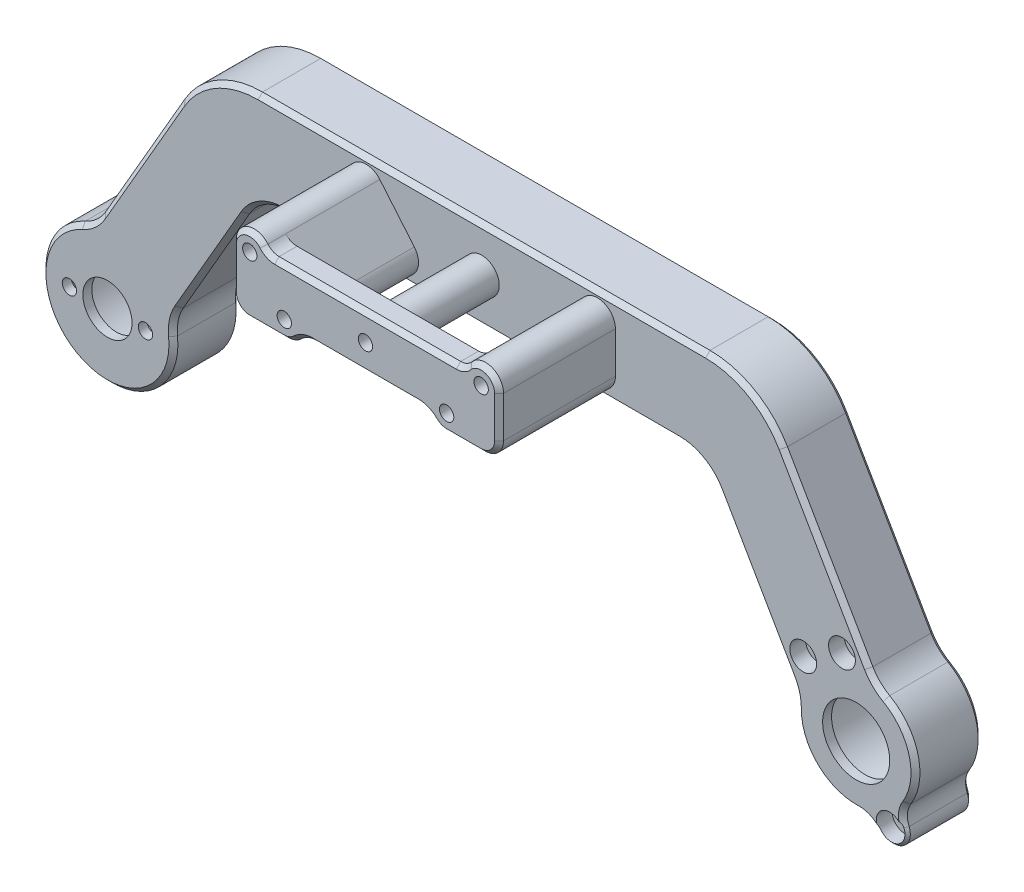
SolidWorks part; units mm, degrees
other "Markup1"
sketch "Sketch2"
ref_plane "Front Plane" through (0, 0, 0) normal (0, 0, 1) x (1, 0, 0)
ref_plane "Top Plane" through (0, 0, 0) normal (0, 1, 0) x (1, 0, 0)
ref_plane "Right Plane" through (0, 0, 0) normal (1, 0, 0) x (0, 0, -1)
ref_axis "X" through (-88.99, 0, 0) along (1, 0, 0)
ref_axis "Y" through (0, 55, 0) along (0, -1, 0)
ref_axis "Z" through (0, 0, -88.99) along (0, 0, 1)
sketch "Sketch1" plane through (0, 0, 0) normal (0, 0, 1) x (1, 0, 0)
  line L0 (0, 10) -> (0, -10) construction
  line L1 (-50, 10) -> (50, 10)
  line L2 (-50, -10) -> (50, -10)
  line L3 (67.3205, 0) -> (92.3205, -43.3013)
  line L4 (75, -53.3013) -> (50, -10)
  line L5 (-75, -53.3013) -> (-50, -10)
  line L6 (-67.3205, 0) -> (-92.3205, -43.3013)
  arc A0 (50, 10) -> (67.3205, 0) centre (50, -10) cw
  arc A1 (92.3205, -43.3013) -> (75, -53.3013) centre (83.6603, -48.3013) cw
  arc A3 (-92.3205, -43.3013) -> (-75, -53.3013) centre (-83.6603, -48.3013) ccw
  arc A4 (-50, 10) -> (-67.3205, 0) centre (-50, -10) ccw
  point P4 (0, 0)
  dimension "D1" = 20
  dimension "D2" = 50
  dimension "D3" = 60
  dimension "D4" = 50
extrude "Boss-Extrude1" add sketch "Sketch1" along normal mid plane 15
ref_plane "Plane1" through (0, 0, 28.5) normal (0, 0, 1) x (1, 0, 0)
sketch "Sketch3" plane through (0, 0, 0) normal (0, 0, 1) x (1, 0, 0)
  line L0 (-22, 0) -> (22, 0) construction
  line L1 (25.8567, 4.5963) -> (18.1433, -4.5963) construction
  line L2 (0, 0) -> (0, 1.6) construction
  line L3 (-25.8567, 4.5963) -> (-18.1433, -4.5963) construction
  circle A1 centre (0, 0) radius 1.6
  circle A2 centre (25.8567, 4.5963) radius 1.6
  circle A3 centre (18.1433, -4.5963) radius 1.6
  circle A4 centre (-25.8567, 4.5963) radius 1.6
  circle A5 centre (-18.1433, -4.5963) radius 1.6
  point P7 (0, 0)
  point P10 (22, 0)
  dimension "D6" = 3.2
  dimension "D3" = 12
  dimension "D4" = 22
  dimension "D5" = 50
extrude "Cut-Extrude1" cut sketch "Sketch3" against normal through all both and the other way through all
sketch "Sketch4" plane through (0, 0, 28.5) normal (0, 0, 1) x (1, 0, 0)
  line L0 (25.8567, 4.5963) -> (18.1433, -4.5963) construction
  line L1 (-25.8567, 4.5963) -> (-18.1433, -4.5963) construction
  line L2 (25.8567, 4.5963) -> (18.1433, -4.5963) construction
  line L3 (-25.8567, 4.5963) -> (-18.1433, -4.5963) construction
  line L4 (15.0791, -2.0251) -> (22.7925, 7.1674)
  line L5 (29.8567, 4.5963) -> (29.8567, -4.5963)
  line L6 (25.8567, -8.5963) -> (18.1433, -8.5963)
  line L7 (0, 0) -> (0, 1.6) construction
  line L8 (0, 0) -> (0, 1.6) construction
  line L9 (-25.8567, -8.5963) -> (-18.1433, -8.5963)
  line L10 (-29.8567, 4.5963) -> (-29.8567, -4.5963)
  line L11 (-15.0791, -2.0251) -> (-22.7925, 7.1674)
  line L12 (20.289, 6) -> (-20.289, 6)
  line L13 (0, 6) -> (0, 3.9)
  line L14 (0, -3.9) -> (0, -6)
  line L15 (-11.8193, -6) -> (11.8193, -6)
  circle A0 centre (25.8567, 4.5963) radius 1.6 construction
  circle A1 centre (18.1433, -4.5963) radius 1.6 construction
  circle A2 centre (-25.8567, 4.5963) radius 1.6 construction
  circle A3 centre (-18.1433, -4.5963) radius 1.6 construction
  circle A4 centre (0, 0) radius 1.6 construction
  circle A5 centre (25.8567, 4.5963) radius 1.6
  circle A6 centre (18.1433, -4.5963) radius 1.6
  circle A7 centre (-25.8567, 4.5963) radius 1.6
  circle A8 centre (-18.1433, -4.5963) radius 1.6
  circle A9 centre (0, 0) radius 1.6
  arc A10 (22.7925, 7.1674) -> (29.8567, 4.5963) centre (25.8567, 4.5963) cw
  arc A11 (29.8567, -4.5963) -> (25.8567, -8.5963) centre (25.8567, -4.5963) cw
  arc A12 (18.1433, -8.5963) -> (15.0791, -2.0251) centre (18.1433, -4.5963) cw
  arc A13 (-29.8567, -4.5963) -> (-25.8567, -8.5963) centre (-25.8567, -4.5963) ccw
  arc A14 (-22.7925, 7.1674) -> (-29.8567, 4.5963) centre (-25.8567, 4.5963) ccw
  arc A15 (-18.1433, -8.5963) -> (-15.0791, -2.0251) centre (-18.1433, -4.5963) ccw
  circle A16 centre (0, 0) radius 3.9
  arc A17 (22.7925, 7.1674) -> (20.289, 6) centre (20.289, 9.2681) cw
  arc A18 (11.8193, -6) -> (15.3326, -7.4424) centre (11.8193, -11) cw
  arc A19 (-11.8193, -6) -> (-15.3326, -7.4424) centre (-11.8193, -11) ccw
  arc A20 (-22.7925, 7.1674) -> (-20.289, 6) centre (-20.289, 9.2681) ccw
  dimension "D1" = 4
  dimension "D4" = 4
  dimension "D5" = 7.8
  dimension "D6" = 12
  dimension "D7" = 5
  dimension "D2" = 4
  dimension "D3" = 4
extrude "Boss-Extrude2" add sketch "Sketch4" against normal up to surface (21 mm away) separate body contours L9 A15 L11 A14 L10 A13 A8 A7 | A12 L6 A11 L5 A10 L4 A6 A5 | A16 A9 region at (23.3022, -1.3358, 28.5) region at (2.6797, 2.6797, 28.5) region at (-23.3022, -1.3358, 28.5) up to face at (-19.7433, -4.5963, 7.5)
extrude "Boss-Extrude3" add sketch "Sketch4<3>" along normal blind 5 contours L9 A15 L11 A14 L10 A13 A8 A7 | A20 L11 A15 A19 L15 L14 A16 L13 L12 | A16 A9 | L15 A18 A12 L4 A17 L12 L13 A16 L14 | A12 L6 A11 L5 A10 L4 A6 A5 region at (9.702, 0.5432, 28.5) region at (23.3022, -1.3358, 28.5) region at (-9.702, 0.5432, 28.5) region at (2.6797, 2.6797, 28.5) region at (-23.3022, -1.3358, 28.5)
sketch "Sketch4<3>" plane through (0, 0, 28.5) normal (0, 0, 1) x (1, 0, 0) same geometry as "Sketch4"
chamfer "Chamfer1" distance 1 angle 45 16 edges at (22, -8.5963, 33.5) (28.6852, -7.4247, 33.5) (16.6241, -8.2966, 33.5) (29.8567, 0, 33.5) (13.7183, -6.3746, 33.5) (27.2248, 8.355, 33.5) (0, -6, 33.5) (21.6702, 6.3062, 33.5) (-13.7183, -6.3746, 33.5) (0, 6, 33.5) (-16.6241, -8.2966, 33.5) (-21.6702, 6.3062, 33.5) (-22, -8.5963, 33.5) (-27.2248, 8.355, 33.5) (-28.6852, -7.4247, 33.5) (-29.8567, 0, 33.5)
sketch "Sketch5" plane through (0, 0, 0) normal (0, 0, 1) x (1, 0, 0)
  line L0 (-92.1603, -48.3013) -> (-75.1603, -48.3013) construction
  circle A1 centre (83.6603, -48.3013) radius 13.25
  circle A3 centre (83.6603, -48.3013) radius 11.25
  circle A4 centre (83.6603, -48.3013) radius 7.5
  circle A5 centre (-83.6603, -48.3013) radius 12.75
  circle A6 centre (-83.6603, -48.3013) radius 14.75
  circle A7 centre (-83.6603, -48.3013) radius 5.5
  circle A8 centre (-75.1603, -48.3013) radius 1.6
  circle A9 centre (-92.1603, -48.3013) radius 1.6
  point P14 (-83.6603, -48.3013)
  dimension "D1" = 2
  dimension "D2" = 22.5
  dimension "D3" = 15
  dimension "D4" = 25.5
  dimension "D6" = 11
  dimension "D8" = 3.2
  dimension "D7" = 17
  dimension "D5" = 2
extrude "Boss-Extrude4" add sketch "Sketch5" along normal up to surface and the other way up to surface contours A1 A3 region at (70.785, -48.3013, 0) up to face at (-19.7433, -4.5963, 7.5) other way up to face at (-19.7433, -4.5963, -7.5)
extrude "Cut-Extrude2" cut sketch "Sketch5<3>" against normal through all both and the other way through all contours A3
sketch "Sketch5<3>" plane through (0, 0, 0) normal (0, 0, 1) x (1, 0, 0) same geometry as "Sketch5"
extrude "Boss-Extrude5" add sketch "Sketch5<4>" against normal blind 2 from surface contours A3 A4 region at (72.7285, -48.3013, 0) starting at face at (72.4103, -48.3013, 7.5)
sketch "Sketch5<4>" plane through (0, 0, 0) normal (0, 0, 1) x (1, 0, 0) same geometry as "Sketch5"
extrude "Cut-Extrude3" cut sketch "Sketch5<5>" against normal through all both and the other way through all contours A5
sketch "Sketch5<5>" plane through (0, 0, 0) normal (0, 0, 1) x (1, 0, 0) same geometry as "Sketch5"
extrude "Boss-Extrude6" add sketch "Sketch5<6>" along normal up to surface (7.5 mm away) and the other way up to surface (7.5 mm away) contours A6 A5 region at (-97.9931, -48.3013, 0) up to face at (1.2608, -17.4619, 7.5) other way up to face at (1.2608, -17.4619, -7.5)
sketch "Sketch5<6>" plane through (0, 0, 0) normal (0, 0, 1) x (1, 0, 0) same geometry as "Sketch5"
extrude "Boss-Extrude7" add sketch "Sketch5<7>" against normal blind 2 from surface contours A5 A9 A7 A8 region at (-96.0496, -48.3013, 0) starting at face at (0.0325, -19.5895, 7.5)
sketch "Sketch5<7>" plane through (0, 0, 0) normal (0, 0, 1) x (1, 0, 0) same geometry as "Sketch5"
fillet "Fillet1" radius 10 6 edges at (87.9742, -35.7732, 0) (70.6537, -45.7732, 0) (-86.8992, -33.9113, 0) (-69.5787, -43.9113, 0) (50, -10, 0) (-50, -10, 0)
sketch "Sketch6" plane through (0, 0, 0) normal (0, 0, 1) x (1, 0, 0)
  line L0 (71.8301, -37.8109) -> (80.4904, -32.8109) construction
  line L1 (76.1603, -35.3109) -> (83.6603, -48.3013) construction
  line L2 (83.6603, -48.3013) -> (91.1603, -61.2917) construction
  line L3 (75, -53.3013) -> (50, -10) construction
  circle A0 centre (91.1603, -61.2917) radius 1.6
  circle A1 centre (80.4904, -32.8109) radius 1.6
  circle A2 centre (71.8301, -37.8109) radius 1.6
  arc A3 (88.3078, -63.488) -> (94.4885, -59.9195) centre (91.1603, -61.2917) ccw
  arc A4 (94.4885, -59.9195) -> (94.878, -55.3529) centre (99.1111, -58.0138) cw
  circle A5 centre (83.6603, -48.3013) radius 13.25 construction
  arc A6 (88.3078, -63.488) -> (84.1582, -61.5419) centre (84.3462, -66.5384) ccw
  arc A7 (84.1582, -61.5419) -> (94.878, -55.3529) centre (83.6603, -48.3013) ccw
  dimension "D4" = 3.2
  dimension "D5" = 2
  dimension "D6" = 5
  dimension "D1" = 10
  dimension "D2" = 15
  dimension "D3" = 15
extrude "Boss-Extrude8" add sketch "Sketch6" along normal up to surface (7.5 mm away) and the other way up to surface (7.5 mm away) contours A7 A6 A3 A4 A0 region at (86.5301, -61.8816, 0) up to face at (0.1801, -23.435, 7.5) other way up to face at (0.1801, -23.435, -7.5)
extrude "Cut-Extrude4" cut sketch "Sketch6<3>" against normal through all both and the other way through all contours A2 | A1 | A0 region at (91.1603, -61.2917, 0) region at (80.4904, -32.8109, 0) region at (71.8301, -37.8109, 0)
sketch "Sketch6<3>" plane through (0, 0, 0) normal (0, 0, 1) x (1, 0, 0) same geometry as "Sketch6"
sketch "Sketch7" plane through (0, 0, 0) normal (0, 0, 1) x (1, 0, 0)
  circle A0 centre (80.4904, -32.8109) radius 3
  circle A1 centre (71.8301, -37.8109) radius 3
  circle A2 centre (91.1603, -61.2917) radius 3
  dimension "D1" = 6
extrude "Cut-Extrude5" cut sketch "Sketch7" against normal blind 3.5 from surface starting at face at (70.2301, -37.8109, 7.5)
chamfer "Chamfer2" distance 1 angle 45 38 edges at (0, -10, -7.5) (49.2265, -11.3397, -7.5) (-49.2265, -11.3397, -7.5) (60.9794, -29.0169, -7.5) (-60.2985, -27.8375, -7.5) (70.0858, -45.5012, -7.5) (-68.8331, -43.6037, -7.5) (-91.0353, -61.0751, -7.5) (88.0225, -35.1454, -7.5) (-87.0056, -33.1118, -7.5) (76.8565, -16.5169, -7.5) (-76.1756, -15.3375, -7.5) (60, 7.3205, -7.5) (-60, 7.3205, -7.5) (0, 10, -7.5) (0, -10, 7.5) (49.2265, -11.3397, 7.5) (-49.2265, -11.3397, 7.5) (60.9794, -29.0169, 7.5) (-60.2985, -27.8375, 7.5) (70.0858, -45.5012, 7.5) (-68.8331, -43.6037, 7.5) (-91.0353, -61.0751, 7.5) (88.0225, -35.1454, 7.5) (-87.0056, -33.1118, 7.5) (76.8565, -16.5169, 7.5) (-76.1756, -15.3375, 7.5) (60, 7.3205, 7.5) (-60, 7.3205, 7.5) (0, 10, 7.5) (86.4692, -62.0115, -7.5) (92.9603, -64.4093, -7.5) (94.1292, -57.5889, -7.5) (96.5024, -45.0391, -7.5) (74.4141, -57.7918, 7.5) (86.4692, -62.0115, 7.5) (92.9603, -64.4093, 7.5) (94.1292, -57.5889, 7.5)
mirror "Mirror1" [suppressed] about plane through (0, 0, 0) normal (0, 0, 1) of bodies 115 106
delete or keep bodies "Body-Delete/Keep 1" [suppressed] type keep bodies bodies 117 116
